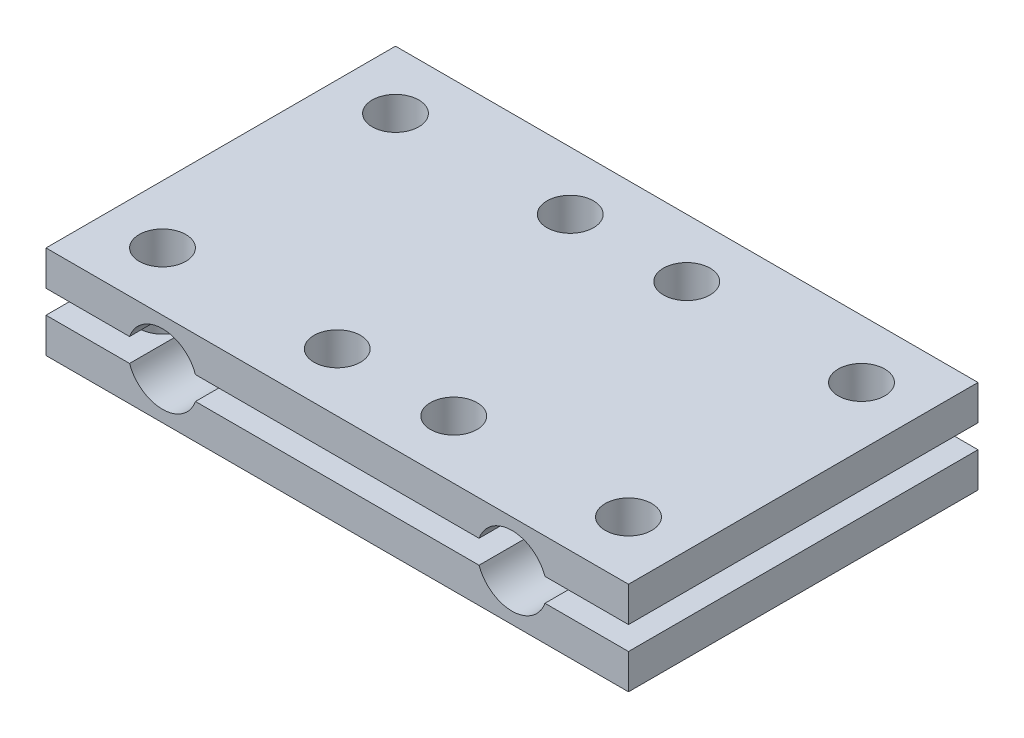
SolidWorks part; units mm, degrees
ref_plane "정면" through (0, 0, 0) normal (0, 0, 1) x (1, 0, 0)
ref_plane "윗면" through (0, 0, 0) normal (0, 1, 0) x (1, 0, 0)
ref_plane "우측면" through (0, 0, 0) normal (1, 0, 0) x (0, 0, -1)
sketch "스케치1" plane through (0, 0, 0) normal (0, 1, 0) x (1, 0, 0)
  line L0 (-12.5, 30) -> (-12.5, 0) construction
  line L1 (0, 0) -> (25, 0)
  line L2 (0, 0) -> (0, 30)
  line L3 (0, 30) -> (25, 30)
  line L4 (25, 0) -> (25, 30)
  line L5 (0, 0) -> (-25, 0)
  line L6 (0, 0) -> (0, 30)
  line L7 (0, 30) -> (-25, 30)
  line L8 (-25, 0) -> (-25, 30)
  line L9 (-20, 30) -> (-20, 0) construction
  line L10 (-25, 15) -> (25, 15) construction
  circle A0 centre (-20, 25) radius 2
  circle A1 centre (-20, 5) radius 2
  circle A2 centre (-5, 5) radius 2
  circle A3 centre (-5, 25) radius 2
  circle A4 centre (5, 5) radius 2
  circle A5 centre (5, 25) radius 2
  circle A6 centre (20, 5) radius 2
  circle A7 centre (20, 25) radius 2
  dimension "D3" = 4
  dimension "D1" = 25
  dimension "D2" = 30
  dimension "D4" = 20
  dimension "D5" = 5
extrude "보스-돌출1" add sketch "스케치1" along normal blind 8 contours L8 L5 L2 L7 A1 A0 A2 A3 | L1 L4 L3 L2 A4 A5 A6 A7 region at (12.5, 0, -15) region at (-12.5, 0, -15)
sketch "스케치2" plane through (0, 0, 0) normal (0, 0, 1) x (1, 0, 0)
  line L0 (0, 0) -> (0, 8) construction
  line L1 (25, 8) -> (-25, 8) construction
  line L2 (-15, 8) -> (-15, 0) construction
  line L3 (15, 8) -> (15, 0) construction
  line L4 (25, 8) -> (25, 0) construction
  line L5 (-25, 5) -> (25, 5)
  line L6 (-25, 5) -> (-25, 3)
  line L7 (-25, 3) -> (25, 3)
  line L8 (25, 5) -> (25, 3)
  line L9 (-25, 5) -> (25, 3) construction
  line L10 (-25, 3) -> (25, 5) construction
  line L11 (25, 5) -> (-25, 3) construction
  line L12 (25, 3) -> (-25, 5) construction
  line L13 (25, 5) -> (25, 3)
  line L14 (-25, 5) -> (-25, 3)
  circle A0 centre (-15, 4) radius 3
  circle A1 centre (15, 4) radius 3
  point P11 (0, 4)
  line M5 (25, 0) -> (25, 8)
  line M7 (-25, 8) -> (-25, 0)
  dimension "D2" = 6
  dimension "D1" = 30
  dimension "D3" = 2
extrude "컷-돌출1" cut sketch "스케치2" against normal through all contours L7 A1 L5 A0 | A0 L5 L7 M7 | L5 A1 L7 M5 | A0 | A1 region at (-21.4716, 4, 0) region at (0, 4, 0) region at (21.4716, 4, 0)
